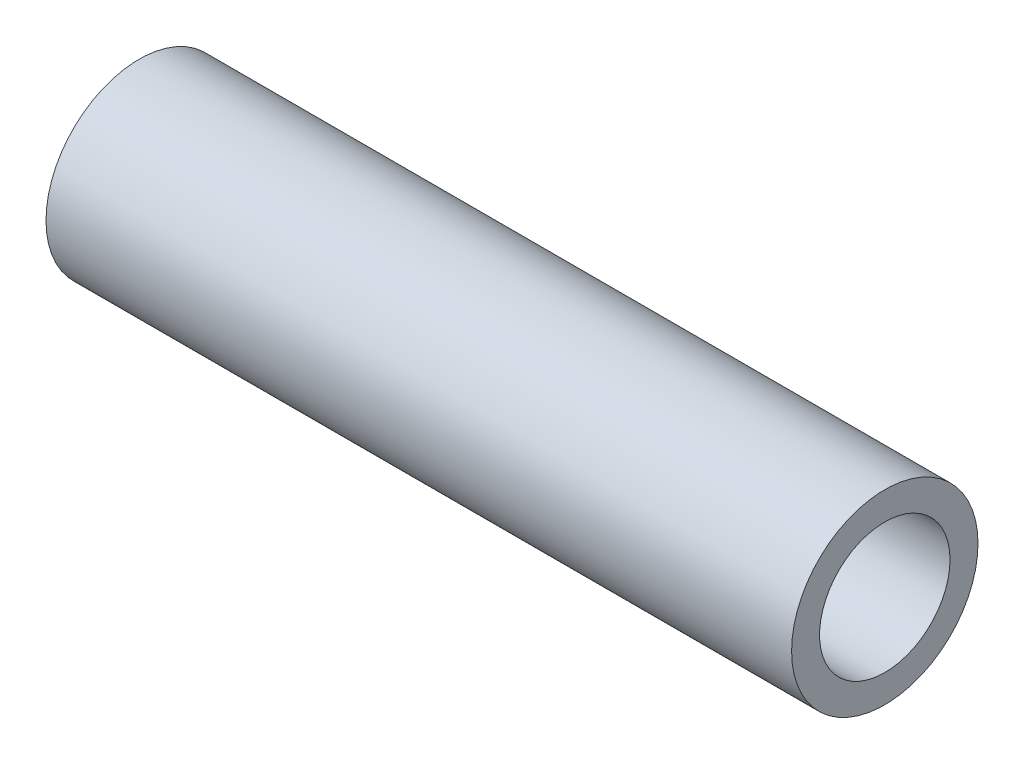
SolidWorks part; units mm, degrees
ref_plane "Alzado" through (0, 0, 0) normal (0, 0, 1) x (1, 0, 0)
ref_plane "Planta" through (0, 0, 0) normal (0, 1, 0) x (1, 0, 0)
ref_plane "Vista lateral" through (0, 0, 0) normal (1, 0, 0) x (0, 0, -1)
sketch "Croquis1" plane through (0, 0, 0) normal (1, 0, 0) x (0, 0, -1)
  circle A0 centre (0, 0) radius 2.5
  circle A1 centre (0, 0) radius 1.75
extrude "Saliente-Extruir1" add sketch "Croquis1" along normal blind 10 and the other way blind 10
